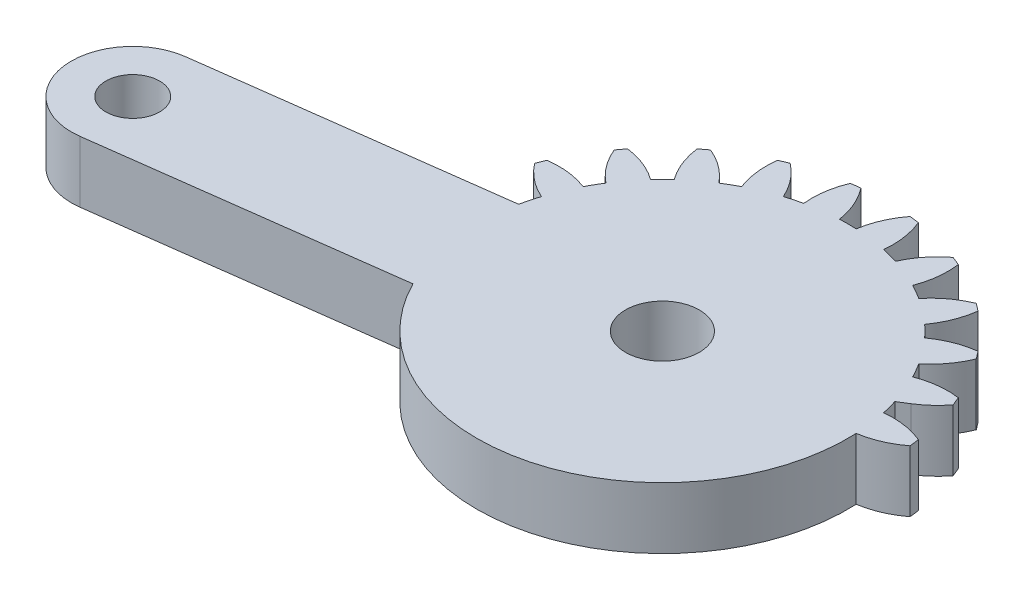
SolidWorks part; units mm, degrees
ref_plane "Front Plane" through (0, 0, 0) normal (0, 0, 1) x (1, 0, 0)
ref_plane "Top Plane" through (0, 0, 0) normal (0, 1, 0) x (1, 0, 0)
ref_plane "Right Plane" through (0, 0, 0) normal (1, 0, 0) x (0, 0, -1)
sketch "Sketch1" plane through (0, 0, 0) normal (0, 1, 0) x (1, 0, 0)
  line L0 (20.6437, 4) -> (2.0816, 4)
  line L1 (2.0816, -4) -> (20.6437, -4)
  arc A0 (2.0816, 4) -> (3.5217, 5.3071) centre (-0.7683, 8.5867) ccw
  arc A1 (3.5217, 5.3071) -> (3.2829, 5.8838) centre (-10.1063, 0) ccw
  arc A2 (3.2829, 5.8838) -> (0.6271, 5.5703) centre (2.5684, 0.5313) ccw
  arc A3 (0.6271, 5.5703) -> (0.0844, 6.5103) centre (-10.1063, 0) ccw
  arc A4 (0.0844, 6.5103) -> (1.6838, 8.6535) centre (-3.3089, 10.711) ccw
  arc A5 (1.6838, 8.6535) -> (1.3038, 9.1487) centre (-10.1063, 0) ccw
  arc A6 (1.3038, 9.1487) -> (-1.1803, 8.1585) centre (1.999, 3.7936) ccw
  arc A7 (-1.1803, 8.1585) -> (-1.9479, 8.926) centre (-10.1063, 0) ccw
  arc A8 (-1.9479, 8.926) -> (-0.9576, 11.4102) centre (-6.3127, 12.1053) ccw
  arc A9 (-0.9576, 11.4102) -> (-1.4528, 11.7901) centre (-10.1063, 0) ccw
  arc A10 (-1.4528, 11.7901) -> (-3.596, 10.1907) centre (0.6046, 6.7975) ccw
  arc A11 (-3.596, 10.1907) -> (-4.5361, 10.7334) centre (-10.1063, 0) ccw
  arc A12 (-4.5361, 10.7334) -> (-4.2225, 13.3892) centre (-9.5751, 12.6747) ccw
  arc A13 (-4.2225, 13.3892) -> (-4.7992, 13.6281) centre (-10.1063, 0) ccw
  arc A14 (-4.7992, 13.6281) -> (-6.4554, 11.5285) centre (-1.5196, 9.3381) ccw
  arc A15 (-6.4554, 11.5285) -> (-7.5039, 11.8094) centre (-10.1063, 0) ccw
  arc A16 (-7.5039, 11.8094) -> (-7.8884, 14.4558) centre (-12.8736, 12.3803) ccw
  arc A17 (-7.8884, 14.4558) -> (-8.5072, 14.5373) centre (-10.1063, 0) ccw
  arc A18 (-8.5072, 14.5373) -> (-9.5636, 12.0806) centre (-4.2291, 11.2423) ccw
  arc A19 (-9.5636, 12.0806) -> (-10.6491, 12.0806) centre (-10.1063, 0) ccw
  arc A20 (-10.6491, 12.0806) -> (-11.7054, 14.5373) centre (-15.9836, 11.2423) ccw
  arc A21 (-11.7054, 14.5373) -> (-12.3243, 14.4558) centre (-10.1063, 0) ccw
  arc A22 (-12.3243, 14.4558) -> (-12.7088, 11.8094) centre (-7.3391, 12.3803) ccw
  arc A23 (-12.7088, 11.8094) -> (-13.7573, 11.5285) centre (-10.1063, 0) ccw
  arc A24 (-13.7573, 11.5285) -> (-15.4135, 13.6281) centre (-18.6931, 9.3381) ccw
  arc A25 (-15.4135, 13.6281) -> (-15.9901, 13.3892) centre (-10.1063, 0) ccw
  arc A26 (-15.9901, 13.3892) -> (-15.6766, 10.7334) centre (-10.6376, 12.6747) ccw
  arc A27 (-15.6766, 10.7334) -> (-16.6166, 10.1907) centre (-10.1063, 0) ccw
  arc A28 (-16.6166, 10.1907) -> (-18.7599, 11.7901) centre (-20.8173, 6.7975) ccw
  arc A29 (-18.7599, 11.7901) -> (-19.255, 11.4102) centre (-10.1063, 0) ccw
  arc A30 (-19.255, 11.4102) -> (-18.2648, 8.926) centre (-13.9, 12.1053) ccw
  arc A31 (-18.2648, 8.926) -> (-19.0324, 8.1585) centre (-10.1063, 0) ccw
  arc A32 (-19.0324, 8.1585) -> (-21.5165, 9.1487) centre (-22.2117, 3.7936) ccw
  arc A33 (-21.5165, 9.1487) -> (-21.8965, 8.6535) centre (-10.1063, 0) ccw
  arc A34 (-21.8965, 8.6535) -> (-20.2971, 6.5103) centre (-16.9038, 10.711) ccw
  arc A35 (-20.2971, 6.5103) -> (-20.8398, 5.5703) centre (-10.1063, 0) ccw
  arc A36 (-20.8398, 5.5703) -> (-23.4956, 5.8838) centre (-22.7811, 0.5313) ccw
  arc A37 (-23.4956, 5.8838) -> (-23.7344, 5.3071) centre (-10.1063, 0) ccw
  arc A38 (-23.7344, 5.3071) -> (-21.6348, 3.6509) centre (-19.4444, 8.5867) ccw
  arc A39 (-21.6348, 3.6509) -> (-21.9157, 2.6025) centre (-10.1063, 0) ccw
  arc A40 (-21.9157, 2.6025) -> (-24.5622, 2.2179) centre (-22.4867, -2.7673) ccw
  arc A41 (-24.5622, 2.2179) -> (-24.6437, 1.5991) centre (-10.1063, 0) ccw
  arc A42 (-24.6437, 1.5991) -> (-22.1869, 0.5427) centre (-21.3486, 5.8773) ccw
  arc A43 (-22.1869, 0.5427) -> (-22.1869, -0.5427) centre (-10.1063, 0) ccw
  arc A44 (-22.1869, -0.5427) -> (-24.6437, -1.5991) centre (-21.3486, -5.8773) ccw
  arc A45 (-24.6437, -1.5991) -> (-24.5622, -2.2179) centre (-10.1063, 0) ccw
  arc A46 (-24.5622, -2.2179) -> (-21.9157, -2.6025) centre (-22.4867, 2.7673) ccw
  arc A47 (-21.9157, -2.6025) -> (-21.6348, -3.6509) centre (-10.1063, 0) ccw
  arc A48 (-21.6348, -3.6509) -> (-23.7344, -5.3071) centre (-19.4444, -8.5867) ccw
  arc A49 (-23.7344, -5.3071) -> (-23.4956, -5.8838) centre (-10.1063, 0) ccw
  arc A50 (-23.4956, -5.8838) -> (-20.8398, -5.5703) centre (-22.7811, -0.5313) ccw
  arc A51 (-20.8398, -5.5703) -> (-20.2971, -6.5103) centre (-10.1063, 0) ccw
  arc A52 (-20.2971, -6.5103) -> (-21.8965, -8.6535) centre (-16.9038, -10.711) ccw
  arc A53 (-21.8965, -8.6535) -> (-21.5165, -9.1487) centre (-10.1063, 0) ccw
  arc A54 (-21.5165, -9.1487) -> (-19.0324, -8.1585) centre (-22.2117, -3.7936) ccw
  arc A55 (-19.0324, -8.1585) -> (-18.2648, -8.926) centre (-10.1063, 0) ccw
  arc A56 (-18.2648, -8.926) -> (-19.255, -11.4102) centre (-13.9, -12.1053) ccw
  arc A57 (-19.255, -11.4102) -> (-18.7599, -11.7901) centre (-10.1063, 0) ccw
  arc A58 (-18.7599, -11.7901) -> (-16.6166, -10.1907) centre (-20.8173, -6.7975) ccw
  arc A59 (-16.6166, -10.1907) -> (-15.6766, -10.7334) centre (-10.1063, 0) ccw
  arc A60 (-15.6766, -10.7334) -> (-15.9901, -13.3892) centre (-10.6376, -12.6747) ccw
  arc A61 (-15.9901, -13.3892) -> (-15.4135, -13.6281) centre (-10.1063, 0) ccw
  arc A62 (-15.4135, -13.6281) -> (-13.7573, -11.5285) centre (-18.6931, -9.3381) ccw
  arc A63 (-13.7573, -11.5285) -> (-12.7088, -11.8094) centre (-10.1063, 0) ccw
  arc A64 (-12.7088, -11.8094) -> (-12.3243, -14.4558) centre (-7.3391, -12.3803) ccw
  arc A65 (-12.3243, -14.4558) -> (-11.7054, -14.5373) centre (-10.1063, 0) ccw
  arc A66 (-11.7054, -14.5373) -> (-10.6491, -12.0806) centre (-15.9836, -11.2423) ccw
  arc A67 (-10.6491, -12.0806) -> (-9.5636, -12.0806) centre (-10.1063, 0) ccw
  arc A68 (-9.5636, -12.0806) -> (-8.5072, -14.5373) centre (-4.2291, -11.2423) ccw
  arc A69 (-8.5072, -14.5373) -> (-7.8884, -14.4558) centre (-10.1063, 0) ccw
  arc A70 (-7.8884, -14.4558) -> (-7.5039, -11.8094) centre (-12.8736, -12.3803) ccw
  arc A71 (-7.5039, -11.8094) -> (-6.4554, -11.5285) centre (-10.1063, 0) ccw
  arc A72 (-6.4554, -11.5285) -> (-4.7992, -13.6281) centre (-1.5196, -9.3381) ccw
  arc A73 (-4.7992, -13.6281) -> (-4.2225, -13.3892) centre (-10.1063, 0) ccw
  arc A74 (-4.2225, -13.3892) -> (-4.5361, -10.7334) centre (-9.5751, -12.6747) ccw
  arc A75 (-4.5361, -10.7334) -> (-3.596, -10.1907) centre (-10.1063, 0) ccw
  arc A76 (-3.596, -10.1907) -> (-1.4528, -11.7901) centre (0.6046, -6.7975) ccw
  arc A77 (-1.4528, -11.7901) -> (-0.9576, -11.4102) centre (-10.1063, 0) ccw
  arc A78 (-0.9576, -11.4102) -> (-1.9479, -8.926) centre (-6.3127, -12.1053) ccw
  arc A79 (-1.9479, -8.926) -> (-1.1803, -8.1585) centre (-10.1063, 0) ccw
  arc A80 (-1.1803, -8.1585) -> (1.3038, -9.1487) centre (1.999, -3.7936) ccw
  arc A81 (1.3038, -9.1487) -> (1.6838, -8.6535) centre (-10.1063, 0) ccw
  arc A82 (1.6838, -8.6535) -> (0.0844, -6.5103) centre (-3.3089, -10.711) ccw
  arc A83 (0.0844, -6.5103) -> (0.6271, -5.5703) centre (-10.1063, 0) ccw
  arc A84 (0.6271, -5.5703) -> (3.2829, -5.8838) centre (2.5684, -0.5313) ccw
  arc A85 (3.2829, -5.8838) -> (3.5217, -5.3071) centre (-10.1063, 0) ccw
  arc A86 (3.5217, -5.3071) -> (2.0816, -4) centre (-0.7683, -8.5867) ccw
  arc A87 (20.6437, -4) -> (20.6437, 4) centre (20.6437, 0) ccw
  circle A88 centre (-10.1063, 0) radius 1.5
  circle A89 centre (20.6437, 0) radius 1.5
  dimension "D1" = 3
  dimension "D2" = 3
extrude "Boss-Extrude1" add sketch "Sketch1" along normal blind 4
sketch "Sketch3" plane through (0, 4, 0) normal (0, 1, 0) x (1, 0, 0)
  line L0 (-10.1063, 0) -> (-40.8563, 0) construction
  line L1 (-10.1063, 0) -> (-40.5933, -4.0137)
  line L2 (-10.6284, 3.9658) -> (-41.1154, -0.0479)
  line L3 (-9.5842, -3.9658) -> (-40.0712, -7.9795)
  line L4 (-10.1063, 0) -> (-4.5096, 13.5117) construction
  line L5 (-10.1063, 0) -> (-8.1974, 14.4999) construction
  circle A0 centre (-10.1063, 0) radius 1.5
  circle A1 centre (20.6437, 0) radius 1.5 construction
  circle A2 centre (20.6437, 0) radius 1.5
  circle A3 centre (-40.5933, -4.0137) radius 1.75
  circle A4 centre (-40.5933, -4.0137) radius 4
  circle A5 centre (-10.1063, 0) radius 4
  arc A6 (-4.2225, 13.3892) -> (-4.7992, 13.6281) centre (-10.1063, 0) ccw construction
  arc A7 (-7.8884, 14.4558) -> (-8.5072, 14.5373) centre (-10.1063, 0) ccw construction
  dimension "D2" = 3
  dimension "D5" = 3.5
  dimension "D6" = 8
  dimension "D7" = 8
  dimension "D1" = 30.75
  dimension "D4" = 7.5
extrude "Boss-Extrude2" add sketch "Sketch3" against normal blind 4 contours L0 A5 L2 | A5 L0 L2 A4 L1 | A4 A3 | A5 L1 A4 L3 | L0 A0 L1 A5 | A0 L0 A5 L1 region at (-13.19, 4, -2.3662) region at (-25.0786, 4, 4.0667) region at (-25.621, 4, -0.053) region at (-36.7147, 4, 3.7595)
sketch "Sketch4" plane through (0, 4, 0) normal (0, 1, 0) x (1, 0, 0)
  line L0 (20.6437, 4) -> (2.0816, 4) construction
  line L1 (2.0816, -4) -> (20.6437, -4) construction
  line L2 (20.6437, 4) -> (2.0816, 4)
  line L3 (2.0816, -4) -> (20.6437, -4)
  line L4 (2.0816, 4) -> (1.4381, 3.6001)
  line L5 (-21.6245, -5.5509) -> (-20.8986, -5.4553)
  line L6 (-10.1063, 0) -> (0.0844, 6.5103) construction
  line L7 (-10.1063, 0) -> (1.9742, 0.5427) construction
  line L8 (-24.5755, 2.1296) -> (-41.1154, -0.0479)
  line L9 (-40.0712, -7.9795) -> (-23.5312, -5.8019)
  line L10 (2.0816, -4) -> (20.6437, -4)
  line L11 (20.6437, 4) -> (2.0816, 4)
  line L12 (-21.9429, 2.4762) -> (-41.1154, -0.0479)
  line L13 (-40.0712, -7.9795) -> (-21.6245, -5.5509)
  line L14 (2.0816, -4) -> (20.6437, -4)
  line L15 (20.6437, 4) -> (2.0816, 4)
  circle A0 centre (-10.1063, 0) radius 12.0927
  arc A1 (3.2829, 5.8838) -> (0.6271, 5.5703) centre (2.5684, 0.5313) ccw construction
  arc A2 (3.5217, 5.3071) -> (3.2829, 5.8838) centre (-10.1063, 0) ccw construction
  arc A3 (2.0816, 4) -> (3.5217, 5.3071) centre (-0.7683, 8.5867) ccw construction
  arc A4 (20.6437, -4) -> (20.6437, 4) centre (20.6437, 0) ccw construction
  arc A5 (3.5217, -5.3071) -> (2.0816, -4) centre (-0.7683, -8.5867) ccw construction
  arc A6 (3.2829, -5.8838) -> (3.5217, -5.3071) centre (-10.1063, 0) ccw construction
  arc A7 (0.6271, -5.5703) -> (3.2829, -5.8838) centre (2.5684, -0.5313) ccw construction
  arc A8 (3.2829, 5.8838) -> (0.6271, 5.5703) centre (2.5684, 0.5313) ccw
  arc A9 (3.5217, 5.3071) -> (3.2829, 5.8838) centre (-10.1063, 0) ccw
  arc A10 (2.0816, 4) -> (3.5217, 5.3071) centre (-0.7683, 8.5867) ccw
  arc A11 (20.6437, -4) -> (20.6437, 4) centre (20.6437, 0) ccw
  arc A12 (3.5217, -5.3071) -> (2.0816, -4) centre (-0.7683, -8.5867) ccw
  arc A13 (3.2829, -5.8838) -> (3.5217, -5.3071) centre (-10.1063, 0) ccw
  arc A14 (0.6271, -5.5703) -> (3.2829, -5.8838) centre (2.5684, -0.5313) ccw
  arc A15 (1.9742, 0.5427) -> (4.431, 1.5991) centre (1.1359, 5.8773) ccw
  arc A16 (4.3495, 2.2179) -> (1.7031, 2.6025) centre (2.274, -2.7673) ccw
  arc A17 (4.431, 1.5991) -> (4.3495, 2.2179) centre (-10.1063, 0) ccw
  arc A95 (-21.6348, 3.6509) -> (-21.9157, 2.6025) centre (-10.1063, 0) ccw
  arc A96 (-41.1154, -0.0479) -> (-40.0712, -7.9795) centre (-40.5933, -4.0137) ccw
  arc A97 (-20.2971, -6.5103) -> (-21.8965, -8.6535) centre (-16.9038, -10.711) ccw
  arc A98 (-21.8965, -8.6535) -> (-21.5165, -9.1487) centre (-10.1063, 0) ccw
  arc A99 (-21.5165, -9.1487) -> (-19.0324, -8.1585) centre (-22.2117, -3.7936) ccw
  arc A100 (-19.0324, -8.1585) -> (-18.2648, -8.926) centre (-10.1063, 0) ccw
  arc A101 (-18.2648, -8.926) -> (-19.255, -11.4102) centre (-13.9, -12.1053) ccw
  arc A102 (-19.255, -11.4102) -> (-18.7599, -11.7901) centre (-10.1063, 0) ccw
  arc A103 (-18.7599, -11.7901) -> (-16.6166, -10.1907) centre (-20.8173, -6.7975) ccw
  arc A104 (-16.6166, -10.1907) -> (-15.6766, -10.7334) centre (-10.1063, 0) ccw
  arc A105 (-15.6766, -10.7334) -> (-15.9901, -13.3892) centre (-10.6376, -12.6747) ccw
  arc A106 (-15.9901, -13.3892) -> (-15.4135, -13.6281) centre (-10.1063, 0) ccw
  arc A107 (-15.4135, -13.6281) -> (-13.7573, -11.5285) centre (-18.6931, -9.3381) ccw
  arc A108 (-13.7573, -11.5285) -> (-12.7088, -11.8094) centre (-10.1063, 0) ccw
  arc A109 (-12.7088, -11.8094) -> (-12.3243, -14.4558) centre (-7.3391, -12.3803) ccw
  arc A110 (-12.3243, -14.4558) -> (-11.7054, -14.5373) centre (-10.1063, 0) ccw
  arc A111 (-11.7054, -14.5373) -> (-10.6491, -12.0806) centre (-15.9836, -11.2423) ccw
  arc A112 (-10.6491, -12.0806) -> (-9.5636, -12.0806) centre (-10.1063, 0) ccw
  arc A113 (-9.5636, -12.0806) -> (-8.5072, -14.5373) centre (-4.2291, -11.2423) ccw
  arc A114 (-8.5072, -14.5373) -> (-7.8884, -14.4558) centre (-10.1063, 0) ccw
  arc A115 (-7.8884, -14.4558) -> (-7.5039, -11.8094) centre (-12.8736, -12.3803) ccw
  arc A116 (-7.5039, -11.8094) -> (-6.4554, -11.5285) centre (-10.1063, 0) ccw
  arc A117 (-6.4554, -11.5285) -> (-4.7992, -13.6281) centre (-1.5196, -9.3381) ccw
  arc A118 (-4.7992, -13.6281) -> (-4.2225, -13.3892) centre (-10.1063, 0) ccw
  arc A119 (-4.2225, -13.3892) -> (-4.5361, -10.7334) centre (-9.5751, -12.6747) ccw
  arc A120 (-4.5361, -10.7334) -> (-3.596, -10.1907) centre (-10.1063, 0) ccw
  arc A121 (-3.596, -10.1907) -> (-1.4528, -11.7901) centre (0.6046, -6.7975) ccw
  arc A122 (-1.4528, -11.7901) -> (-0.9576, -11.4102) centre (-10.1063, 0) ccw
  arc A123 (-0.9576, -11.4102) -> (-1.9479, -8.926) centre (-6.3127, -12.1053) ccw
  arc A124 (-1.9479, -8.926) -> (-1.1803, -8.1585) centre (-10.1063, 0) ccw
  arc A125 (-1.1803, -8.1585) -> (1.3038, -9.1487) centre (1.999, -3.7936) ccw
  arc A126 (1.3038, -9.1487) -> (1.6838, -8.6535) centre (-10.1063, 0) ccw
  arc A127 (1.6838, -8.6535) -> (0.0844, -6.5103) centre (-3.3089, -10.711) ccw
  arc A128 (0.0844, -6.5103) -> (0.6271, -5.5703) centre (-10.1063, 0) ccw
  arc A129 (0.6271, -5.5703) -> (3.2829, -5.8838) centre (2.5684, -0.5313) ccw
  arc A130 (3.2829, -5.8838) -> (3.5217, -5.3071) centre (-10.1063, 0) ccw
  arc A131 (3.5217, -5.3071) -> (2.0816, -4) centre (-0.7683, -8.5867) ccw
  arc A132 (20.6437, -4) -> (20.6437, 4) centre (20.6437, 0) ccw
  arc A133 (2.0816, 4) -> (3.5217, 5.3071) centre (-0.7683, 8.5867) ccw
  arc A134 (3.5217, 5.3071) -> (3.2829, 5.8838) centre (-10.1063, 0) ccw
  arc A135 (3.2829, 5.8838) -> (0.6271, 5.5703) centre (2.5684, 0.5313) ccw
  arc A136 (0.6271, 5.5703) -> (0.0844, 6.5103) centre (-10.1063, 0) ccw
  arc A137 (0.0844, 6.5103) -> (1.6838, 8.6535) centre (-3.3089, 10.711) ccw
  arc A138 (1.6838, 8.6535) -> (1.3038, 9.1487) centre (-10.1063, 0) ccw
  arc A139 (1.3038, 9.1487) -> (-1.1803, 8.1585) centre (1.999, 3.7936) ccw
  arc A140 (-1.1803, 8.1585) -> (-1.9479, 8.926) centre (-10.1063, 0) ccw
  arc A141 (-1.9479, 8.926) -> (-0.9576, 11.4102) centre (-6.3127, 12.1053) ccw
  arc A142 (-0.9576, 11.4102) -> (-1.4528, 11.7901) centre (-10.1063, 0) ccw
  arc A143 (-1.4528, 11.7901) -> (-3.596, 10.1907) centre (0.6046, 6.7975) ccw
  arc A144 (-3.596, 10.1907) -> (-4.5361, 10.7334) centre (-10.1063, 0) ccw
  arc A145 (-4.5361, 10.7334) -> (-4.2225, 13.3892) centre (-9.5751, 12.6747) ccw
  arc A146 (-4.2225, 13.3892) -> (-4.7992, 13.6281) centre (-10.1063, 0) ccw
  arc A147 (-4.7992, 13.6281) -> (-6.4554, 11.5285) centre (-1.5196, 9.3381) ccw
  arc A148 (-6.4554, 11.5285) -> (-7.5039, 11.8094) centre (-10.1063, 0) ccw
  arc A149 (-7.5039, 11.8094) -> (-7.8884, 14.4558) centre (-12.8736, 12.3803) ccw
  arc A150 (-7.8884, 14.4558) -> (-8.5072, 14.5373) centre (-10.1063, 0) ccw
  arc A151 (-8.5072, 14.5373) -> (-9.5636, 12.0806) centre (-4.2291, 11.2423) ccw
  arc A152 (-9.5636, 12.0806) -> (-10.6491, 12.0806) centre (-10.1063, 0) ccw
  arc A153 (-10.6491, 12.0806) -> (-11.7054, 14.5373) centre (-15.9836, 11.2423) ccw
  arc A154 (-11.7054, 14.5373) -> (-12.3243, 14.4558) centre (-10.1063, 0) ccw
  arc A155 (-12.3243, 14.4558) -> (-12.7088, 11.8094) centre (-7.3391, 12.3803) ccw
  arc A156 (-12.7088, 11.8094) -> (-13.7573, 11.5285) centre (-10.1063, 0) ccw
  arc A157 (-13.7573, 11.5285) -> (-15.4135, 13.6281) centre (-18.6931, 9.3381) ccw
  arc A158 (-15.4135, 13.6281) -> (-15.9901, 13.3892) centre (-10.1063, 0) ccw
  arc A159 (-15.9901, 13.3892) -> (-15.6766, 10.7334) centre (-10.6376, 12.6747) ccw
  arc A160 (-15.6766, 10.7334) -> (-16.6166, 10.1907) centre (-10.1063, 0) ccw
  arc A161 (-16.6166, 10.1907) -> (-18.7599, 11.7901) centre (-20.8173, 6.7975) ccw
  arc A162 (-18.7599, 11.7901) -> (-19.255, 11.4102) centre (-10.1063, 0) ccw
  arc A163 (-19.255, 11.4102) -> (-18.2648, 8.926) centre (-13.9, 12.1053) ccw
  arc A164 (-18.2648, 8.926) -> (-19.0324, 8.1585) centre (-10.1063, 0) ccw
  arc A165 (-19.0324, 8.1585) -> (-21.5165, 9.1487) centre (-22.2117, 3.7936) ccw
  arc A166 (-21.5165, 9.1487) -> (-21.8965, 8.6535) centre (-10.1063, 0) ccw
  arc A167 (-21.8965, 8.6535) -> (-20.2971, 6.5103) centre (-16.9038, 10.711) ccw
  arc A168 (-20.2971, 6.5103) -> (-20.8398, 5.5703) centre (-10.1063, 0) ccw
  arc A169 (-20.8398, 5.5703) -> (-23.4956, 5.8838) centre (-22.7811, 0.5313) ccw
  arc A170 (-23.4956, 5.8838) -> (-23.7344, 5.3071) centre (-10.1063, 0) ccw
  arc A171 (-23.7344, 5.3071) -> (-21.6348, 3.6509) centre (-19.4444, 8.5867) ccw
  arc A172 (-21.6348, 3.6509) -> (-21.9157, 2.6025) centre (-10.1063, 0) ccw
  arc A175 (-23.4956, -5.8838) -> (-20.8398, -5.5703) centre (-22.7811, -0.5313) ccw
  arc A176 (-41.1154, -0.0479) -> (-40.0712, -7.9795) centre (-40.5933, -4.0137) ccw
  arc A177 (-20.2971, -6.5103) -> (-21.8965, -8.6535) centre (-16.9038, -10.711) ccw
  arc A178 (-21.8965, -8.6535) -> (-21.5165, -9.1487) centre (-10.1063, 0) ccw
  arc A179 (-21.5165, -9.1487) -> (-19.0324, -8.1585) centre (-22.2117, -3.7936) ccw
  arc A180 (-19.0324, -8.1585) -> (-18.2648, -8.926) centre (-10.1063, 0) ccw
  arc A181 (-18.2648, -8.926) -> (-19.255, -11.4102) centre (-13.9, -12.1053) ccw
  arc A182 (-19.255, -11.4102) -> (-18.7599, -11.7901) centre (-10.1063, 0) ccw
  arc A183 (-18.7599, -11.7901) -> (-16.6166, -10.1907) centre (-20.8173, -6.7975) ccw
  arc A184 (-16.6166, -10.1907) -> (-15.6766, -10.7334) centre (-10.1063, 0) ccw
  arc A185 (-15.6766, -10.7334) -> (-15.9901, -13.3892) centre (-10.6376, -12.6747) ccw
  arc A186 (-15.9901, -13.3892) -> (-15.4135, -13.6281) centre (-10.1063, 0) ccw
  arc A187 (-15.4135, -13.6281) -> (-13.7573, -11.5285) centre (-18.6931, -9.3381) ccw
  arc A188 (-13.7573, -11.5285) -> (-12.7088, -11.8094) centre (-10.1063, 0) ccw
  arc A189 (-12.7088, -11.8094) -> (-12.3243, -14.4558) centre (-7.3391, -12.3803) ccw
  arc A190 (-12.3243, -14.4558) -> (-11.7054, -14.5373) centre (-10.1063, 0) ccw
  arc A191 (-11.7054, -14.5373) -> (-10.6491, -12.0806) centre (-15.9836, -11.2423) ccw
  arc A192 (-10.6491, -12.0806) -> (-9.5636, -12.0806) centre (-10.1063, 0) ccw
  arc A193 (-9.5636, -12.0806) -> (-8.5072, -14.5373) centre (-4.2291, -11.2423) ccw
  arc A194 (-8.5072, -14.5373) -> (-7.8884, -14.4558) centre (-10.1063, 0) ccw
  arc A195 (-7.8884, -14.4558) -> (-7.5039, -11.8094) centre (-12.8736, -12.3803) ccw
  arc A196 (-7.5039, -11.8094) -> (-6.4554, -11.5285) centre (-10.1063, 0) ccw
  arc A197 (-6.4554, -11.5285) -> (-4.7992, -13.6281) centre (-1.5196, -9.3381) ccw
  arc A198 (-4.7992, -13.6281) -> (-4.2225, -13.3892) centre (-10.1063, 0) ccw
  arc A199 (-4.2225, -13.3892) -> (-4.5361, -10.7334) centre (-9.5751, -12.6747) ccw
  arc A200 (-4.5361, -10.7334) -> (-3.596, -10.1907) centre (-10.1063, 0) ccw
  arc A201 (-3.596, -10.1907) -> (-1.4528, -11.7901) centre (0.6046, -6.7975) ccw
  arc A202 (-1.4528, -11.7901) -> (-0.9576, -11.4102) centre (-10.1063, 0) ccw
  arc A203 (-0.9576, -11.4102) -> (-1.9479, -8.926) centre (-6.3127, -12.1053) ccw
  arc A204 (-1.9479, -8.926) -> (-1.1803, -8.1585) centre (-10.1063, 0) ccw
  arc A205 (-1.1803, -8.1585) -> (1.3038, -9.1487) centre (1.999, -3.7936) ccw
  arc A206 (1.3038, -9.1487) -> (1.6838, -8.6535) centre (-10.1063, 0) ccw
  arc A207 (1.6838, -8.6535) -> (0.0844, -6.5103) centre (-3.3089, -10.711) ccw
  arc A208 (0.0844, -6.5103) -> (0.6271, -5.5703) centre (-10.1063, 0) ccw
  arc A209 (0.6271, -5.5703) -> (3.2829, -5.8838) centre (2.5684, -0.5313) ccw
  arc A210 (3.2829, -5.8838) -> (3.5217, -5.3071) centre (-10.1063, 0) ccw
  arc A211 (3.5217, -5.3071) -> (2.0816, -4) centre (-0.7683, -8.5867) ccw
  arc A212 (20.6437, -4) -> (20.6437, 4) centre (20.6437, 0) ccw
  arc A213 (2.0816, 4) -> (3.5217, 5.3071) centre (-0.7683, 8.5867) ccw
  arc A214 (3.5217, 5.3071) -> (3.2829, 5.8838) centre (-10.1063, 0) ccw
  arc A215 (3.2829, 5.8838) -> (0.6271, 5.5703) centre (2.5684, 0.5313) ccw
  arc A216 (0.6271, 5.5703) -> (0.0844, 6.5103) centre (-10.1063, 0) ccw
  arc A217 (0.0844, 6.5103) -> (1.6838, 8.6535) centre (-3.3089, 10.711) ccw
  arc A218 (1.6838, 8.6535) -> (1.3038, 9.1487) centre (-10.1063, 0) ccw
  arc A219 (1.3038, 9.1487) -> (-1.1803, 8.1585) centre (1.999, 3.7936) ccw
  arc A220 (-1.1803, 8.1585) -> (-1.9479, 8.926) centre (-10.1063, 0) ccw
  arc A221 (-1.9479, 8.926) -> (-0.9576, 11.4102) centre (-6.3127, 12.1053) ccw
  arc A222 (-0.9576, 11.4102) -> (-1.4528, 11.7901) centre (-10.1063, 0) ccw
  arc A223 (-1.4528, 11.7901) -> (-3.596, 10.1907) centre (0.6046, 6.7975) ccw
  arc A224 (-3.596, 10.1907) -> (-4.5361, 10.7334) centre (-10.1063, 0) ccw
  arc A225 (-4.5361, 10.7334) -> (-4.2225, 13.3892) centre (-9.5751, 12.6747) ccw
  arc A226 (-4.2225, 13.3892) -> (-4.7992, 13.6281) centre (-10.1063, 0) ccw
  arc A227 (-4.7992, 13.6281) -> (-6.4554, 11.5285) centre (-1.5196, 9.3381) ccw
  arc A228 (-6.4554, 11.5285) -> (-7.5039, 11.8094) centre (-10.1063, 0) ccw
  arc A229 (-7.5039, 11.8094) -> (-7.8884, 14.4558) centre (-12.8736, 12.3803) ccw
  arc A230 (-7.8884, 14.4558) -> (-8.5072, 14.5373) centre (-10.1063, 0) ccw
  arc A231 (-8.5072, 14.5373) -> (-9.5636, 12.0806) centre (-4.2291, 11.2423) ccw
  arc A232 (-9.5636, 12.0806) -> (-10.6491, 12.0806) centre (-10.1063, 0) ccw
  arc A233 (-10.6491, 12.0806) -> (-11.7054, 14.5373) centre (-15.9836, 11.2423) ccw
  arc A234 (-11.7054, 14.5373) -> (-12.3243, 14.4558) centre (-10.1063, 0) ccw
  arc A235 (-12.3243, 14.4558) -> (-12.7088, 11.8094) centre (-7.3391, 12.3803) ccw
  arc A236 (-12.7088, 11.8094) -> (-13.7573, 11.5285) centre (-10.1063, 0) ccw
  arc A237 (-13.7573, 11.5285) -> (-15.4135, 13.6281) centre (-18.6931, 9.3381) ccw
  arc A238 (-15.4135, 13.6281) -> (-15.9901, 13.3892) centre (-10.1063, 0) ccw
  arc A239 (-15.9901, 13.3892) -> (-15.6766, 10.7334) centre (-10.6376, 12.6747) ccw
  arc A240 (-15.6766, 10.7334) -> (-16.6166, 10.1907) centre (-10.1063, 0) ccw
  arc A241 (-16.6166, 10.1907) -> (-18.7599, 11.7901) centre (-20.8173, 6.7975) ccw
  arc A242 (-18.7599, 11.7901) -> (-19.255, 11.4102) centre (-10.1063, 0) ccw
  arc A243 (-19.255, 11.4102) -> (-18.2648, 8.926) centre (-13.9, 12.1053) ccw
  arc A244 (-18.2648, 8.926) -> (-19.0324, 8.1585) centre (-10.1063, 0) ccw
  arc A245 (-19.0324, 8.1585) -> (-21.5165, 9.1487) centre (-22.2117, 3.7936) ccw
  arc A246 (-21.5165, 9.1487) -> (-21.8965, 8.6535) centre (-10.1063, 0) ccw
  arc A247 (-21.8965, 8.6535) -> (-20.2971, 6.5103) centre (-16.9038, 10.711) ccw
  arc A248 (-20.2971, 6.5103) -> (-20.8398, 5.5703) centre (-10.1063, 0) ccw
  arc A249 (-20.8398, 5.5703) -> (-23.4956, 5.8838) centre (-22.7811, 0.5313) ccw
  arc A250 (-23.4956, 5.8838) -> (-23.7344, 5.3071) centre (-10.1063, 0) ccw
  arc A251 (-23.7344, 5.3071) -> (-21.6348, 3.6509) centre (-19.4444, 8.5867) ccw
  arc A252 (-23.4956, -5.8838) -> (-20.8398, -5.5703) centre (-22.7811, -0.5313) ccw
  arc A253 (-20.8398, -5.5703) -> (-20.2971, -6.5103) centre (-10.1063, 0) ccw
  arc A254 (-20.8398, -5.5703) -> (-20.2971, -6.5103) centre (-10.1063, 0) ccw
  arc A255 (-23.5312, -5.8019) -> (-23.4956, -5.8838) centre (-10.1063, 0) ccw
  arc A256 (-23.5312, -5.8019) -> (-23.4956, -5.8838) centre (-10.1063, 0) ccw
  arc A257 (-21.9157, 2.6025) -> (-24.5622, 2.2179) centre (-22.4867, -2.7673) ccw
  arc A258 (-21.9157, 2.6025) -> (-24.5622, 2.2179) centre (-22.4867, -2.7673) ccw
  arc A259 (-24.5622, 2.2179) -> (-24.5755, 2.1296) centre (-10.1063, 0) ccw
  arc A260 (-24.5622, 2.2179) -> (-24.5755, 2.1296) centre (-10.1063, 0) ccw
  point P40 (-10.1063, 0)
  dimension "D2" = 24.1855
  dimension "D4" = 30
  dimension "D1" = 0
  dimension "D3" = 2
extrude "Cut-Extrude1" cut sketch "Sketch4" against normal blind 4 contours A178 A179 A0 L5 A177 | A182 A183 A0 A181 | A186 A187 A0 A185 | A190 A191 A0 A189 | A194 A195 A0 A193 | A198 A199 A0 A197 | A202 A203 A0 A201 | A206 A207 A0 A205 | A258 A260 L12 A0 | L13 A256 A252 A0 L5 | A0 A14 A13 A12 L3 A11 L2 L4 region at (12.7894, 4, 0.1545) region at (0.3325, 4, 8.01) region at (-2.0963, 4, 10.4389) region at (-5.071, 4, 12.1563) region at (-8.3889, 4, 13.0454) region at (-11.8238, 4, 13.0454) region at (-15.1417, 4, 12.1563) region at (-18.1164, 4, 10.4389) region at (-20.5452, 4, 8.01) region at (-23.2126, 4, -2.4243) region at (-22.1386, 4, 5.7339)
sketch "Sketch5" plane through (0, 4, 0) normal (0, 1, 0) x (1, 0, 0)
  circle A0 centre (-10.1063, 0) radius 2.4
  dimension "D1" = 4.8
extrude "Cut-Extrude2" cut sketch "Sketch5" against normal up to next contours A0
